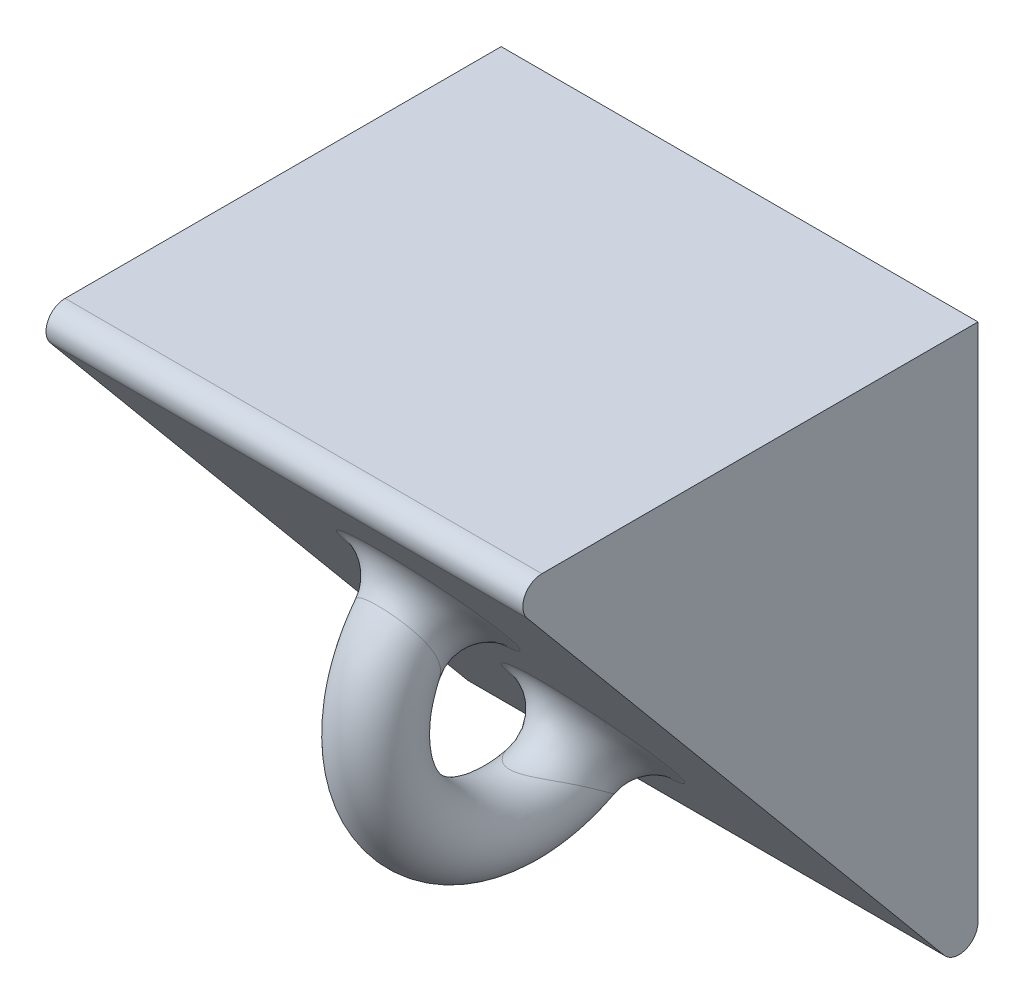
SolidWorks part; units mm, degrees
ref_plane "Front Plane" through (0, 0, 0) normal (0, 0, 1) x (1, 0, 0)
ref_plane "Top Plane" through (0, 0, 0) normal (0, 1, 0) x (1, 0, 0)
ref_plane "Right Plane" through (0, 0, 0) normal (1, 0, 0) x (0, 0, -1)
sketch "Sketch1" plane through (0, 0, 0) normal (1, 0, 0) x (0, 0, -1)
  line L2 (0, 0) -> (25, 0)
  line L3 (25, 0) -> (25, -30)
  line L4 (0, 0) -> (25, -30)
  point P0 (0, 0)
  dimension "D1" = 25
  dimension "D2" = 30
extrude "Boss-Extrude1" add sketch "Sketch1" along normal blind 25
fillet "Fillet1" radius 1 2 edges at (12.5, -30, -25) (12.5, 0, 0)
sketch "Sketch3" plane through (0, 0, 0) normal (0, -0.6402, 0.7682) x (1, 0, 0)
  line L0 (0, -36.2892) -> (25, -36.2892) construction
  line L1 (0, -19.2121) -> (25, -19.2121) construction
  line L2 (0, -2.135) -> (0, -36.2892) construction
  line L3 (25, -2.135) -> (25, -36.2892) construction
  circle A0 centre (13.1958, -26.2892) radius 2
  dimension "D1" = 4
  dimension "D2" = 10
revolve "Revolve1" add sketch "Sketch3" angle 180 about L1 reverse direction yes
fillet "Fillet2" radius 2 2 edges at (13.1958, -7.786, -6.4883) (13.1958, -18.6595, -15.5496)
